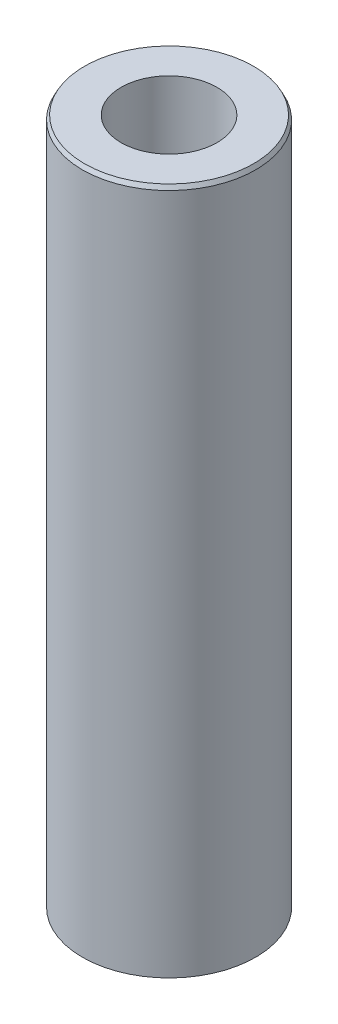
SolidWorks part; units mm, degrees
ref_plane "Front Plane" through (0, 0, 0) normal (0, 0, 1) x (1, 0, 0)
ref_plane "Top Plane" through (0, 0, 0) normal (0, 1, 0) x (1, 0, 0)
ref_plane "Right Plane" through (0, 0, 0) normal (1, 0, 0) x (0, 0, -1)
sketch "Sketch1" plane through (0, 0, 0) normal (0, 1, 0) x (1, 0, 0)
  circle A0 centre (0, 0) radius 37.5
  dimension "SHAFT_OD" = 75
extrude "Boss-Extrude1" add sketch "Sketch1" along normal blind 297.808
sketch "Sketch2" plane through (0, 0, 0) normal (0, 1, 0) x (1, 0, 0)
  circle A0 centre (0, 0) radius 20.7644
  dimension "BORE_D" = 41.5288
extrude "Cut-Extrude1" cut sketch "Sketch2" along normal through all
chamfer "Chamfer1" distance 1.8109 angle 27.246 2 edges at (0, 297.808, 37.5) (0, 0, 37.5) first distance on face at (0, 297.808, 37.5) first distance on face at (0, 0, 20.7644)
